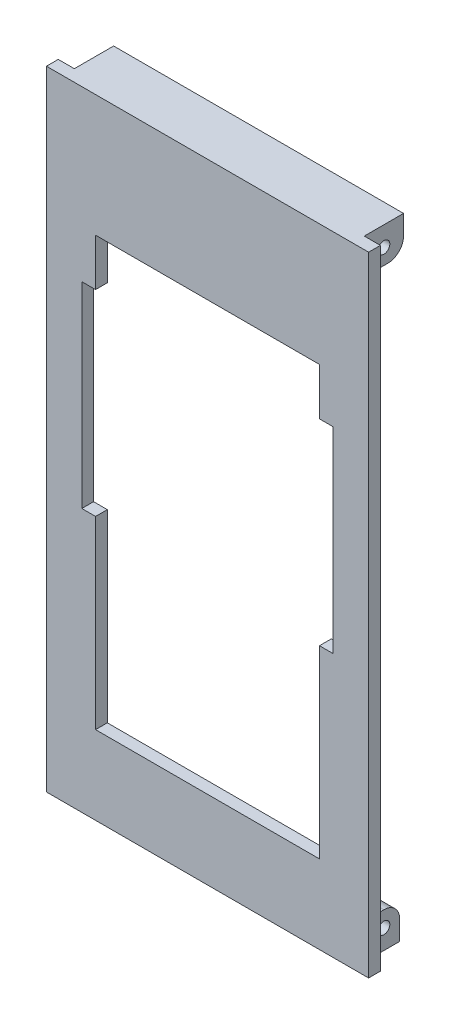
SolidWorks part; units mm, degrees
ref_plane "Front Plane" through (0, 0, 0) normal (0, 0, 1) x (1, 0, 0)
ref_plane "Top Plane" through (0, 0, 0) normal (0, 1, 0) x (1, 0, 0)
ref_plane "Right Plane" through (0, 0, 0) normal (1, 0, 0) x (0, 0, -1)
sketch "Sketch3" plane through (0, 0, 0) normal (1, 0, 0) x (0, 0, -1)
  line L0 (0, 160) -> (13, 160)
  line L2 (0, 0) -> (0, 160)
  line L4 (3, 9) -> (3, 151)
  line L7 (3, 151) -> (13, 151)
  line L8 (13, 160) -> (13, 151)
  line L11 (3, 9) -> (12, 9)
  line L12 (12, 0) -> (12, 9)
  line L13 (0, 0) -> (12, 0)
  circle A0 centre (8, 155) radius 1.5
  circle A1 centre (8, 5) radius 1.5
  dimension "D2" = 3
  dimension "D3" = 3
  dimension "D1" = 3
  dimension "D4" = 160
  dimension "D5" = 5
  dimension "D6" = 8
  dimension "D7" = 4
  dimension "D8" = 4
  dimension "D9" = 5
  dimension "D10" = 8
  dimension "D11" = 4
  dimension "D12" = 5
extrude "Boss-Extrude3" add sketch "Sketch3" along normal blind 82 separate body
sketch "Sketch4" plane through (0, 0, 0) normal (0, 0, 1) x (1, 0, 0)
  line L0 (0, 0) -> (82, 0) construction
  line L1 (41, 0) -> (41, 184) construction
  line L2 (12.5, 117) -> (12.5, 129)
  line L3 (12.5, 20) -> (69.5, 20)
  line L4 (12.5, 20) -> (12.5, 67)
  line L5 (12.5, 129) -> (69.5, 129)
  line L6 (69.5, 20) -> (69.5, 67)
  line L7 (12.5, 20) -> (69.5, 129) construction
  line L8 (12.5, 129) -> (69.5, 20) construction
  line L9 (9, 67) -> (12.5, 67)
  line L10 (9, 67) -> (9, 117)
  line L11 (9, 117) -> (12.5, 117)
  line L12 (73, 67) -> (73, 117)
  line L13 (9, 67) -> (73, 117) construction
  line L14 (9, 117) -> (73, 67) construction
  line L15 (69.5, 117) -> (73, 117)
  line L16 (69.5, 117) -> (69.5, 129)
  line L17 (69.5, 67) -> (73, 67)
  line L18 (82, 160) -> (0, 160) construction
  point P6 (41, 74.5)
  point P11 (41, 92)
  dimension "D1" = 31
  dimension "D2" = 20
  dimension "D3" = 3.5
  dimension "D4" = 12
  dimension "D5" = 50
  dimension "D6" = 57
extrude "Cut-Extrude1" cut sketch "Sketch4" against normal through all
sketch "Sketch5" plane through (0, 0, 0) normal (0, 1, 0) x (1, 0, 0)
  line L0 (0, 0) -> (82, 0) construction
  line L1 (82, 3) -> (77.9, 3)
  line L2 (41, 0) -> (41, 22.0256) construction
  line L3 (0, 15) -> (4.1, 15)
  line L4 (0, 15) -> (0, 3)
  line L5 (0, 3) -> (4.1, 3)
  line L6 (4.1, 15) -> (4.1, 3)
  line L7 (77.9, 15) -> (77.9, 3)
  line L8 (82, 15) -> (77.9, 15)
  line L9 (82, 15) -> (82, 3)
  dimension "D1" = 3
  dimension "D2" = 4.1
  dimension "D3" = 12
extrude "Cut-Extrude2" cut sketch "Sketch5" along normal through all contours L4 L5 L6 L3 | L1 L7 L8 L9
fillet "Fillet1" radius 4 2 edges at (41, 151, -13) (41, 9, -12)
